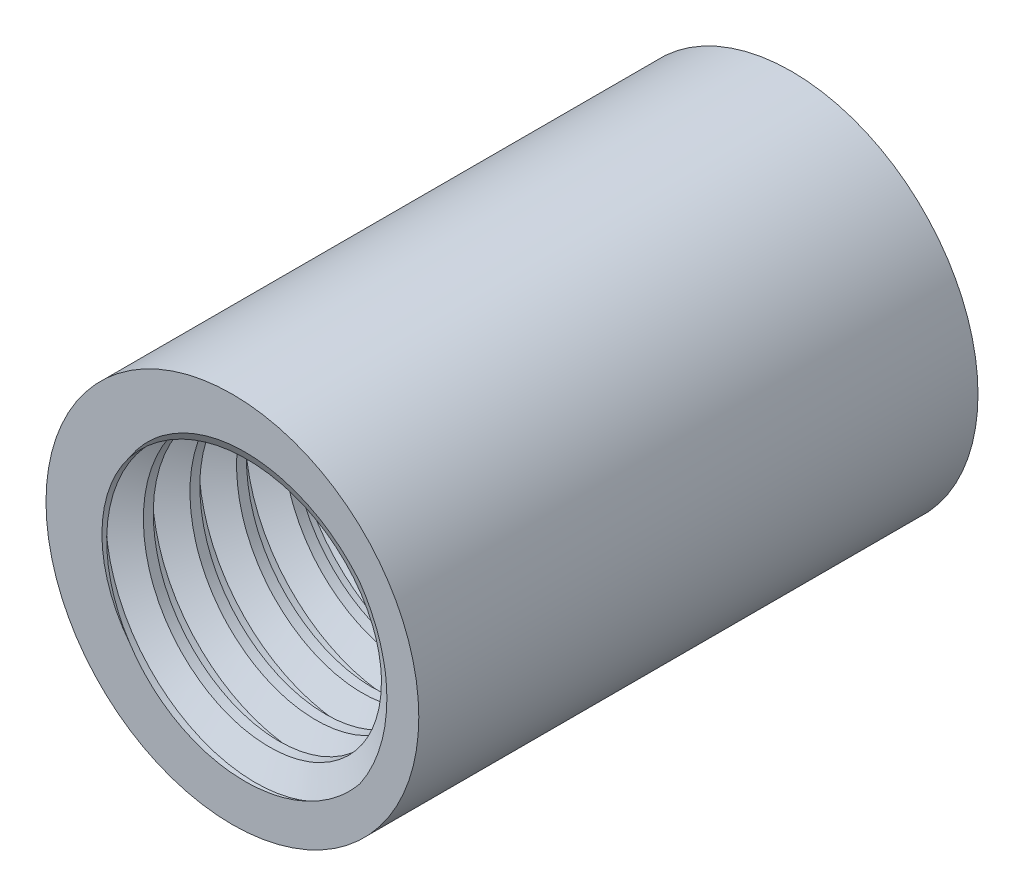
SolidWorks part; units mm, degrees
ref_plane "Front Plane" through (0, 0, 0) normal (0, 0, 1) x (1, 0, 0)
ref_plane "Top Plane" through (0, 0, 0) normal (0, 1, 0) x (1, 0, 0)
ref_plane "Right Plane" through (0, 0, 0) normal (1, 0, 0) x (0, 0, -1)
sketch "Sketch1" plane through (0, 0, 0) normal (0, 0, 1) x (1, 0, 0)
  circle A0 centre (0, 0) radius 6.35
  dimension "D1" = 12.7
extrude "Boss-Extrude1" add sketch "Sketch1" along normal blind 19.05
sketch "Sketch2" plane through (0, 0, 0) normal (0, 0, 1) x (1, 0, 0)
  circle A0 centre (0, 0) radius 4.445
  dimension "D1" = 8.89
extrude "Cut-Extrude1" cut sketch "Sketch2" along normal through all contours A0
sketch "Sketch3" plane through (0, 0, 0) normal (0, 0, 1) x (1, 0, 0)
  circle A0 centre (0, 0) radius 4.445
  dimension "D1" = 8.89
curve "Helix/Spiral1" pitch 1.5875 height 25.4 turns 16
sketch "Sketch4" plane through (0, 0, 0) normal (0, 1, 0) x (1, 0, 0)
  line L0 (4.445, -0.6248) -> (4.445, 0.6248)
  line L1 (5.2633, 0.1524) -> (5.2633, -0.1524)
  line L2 (5.2633, 0.1524) -> (4.445, 0.6248)
  line L3 (5.2633, -0.1524) -> (4.445, -0.6248)
  point P4 (4.445, 0)
  point P5 (4.445, 0)
  dimension "D1" = 1.2497
  dimension "D2" = 0.3048
  dimension "D4" = 60
sweep "Cut-Sweep1" cut profiles "Sketch4" path "Helix/Spiral1"
